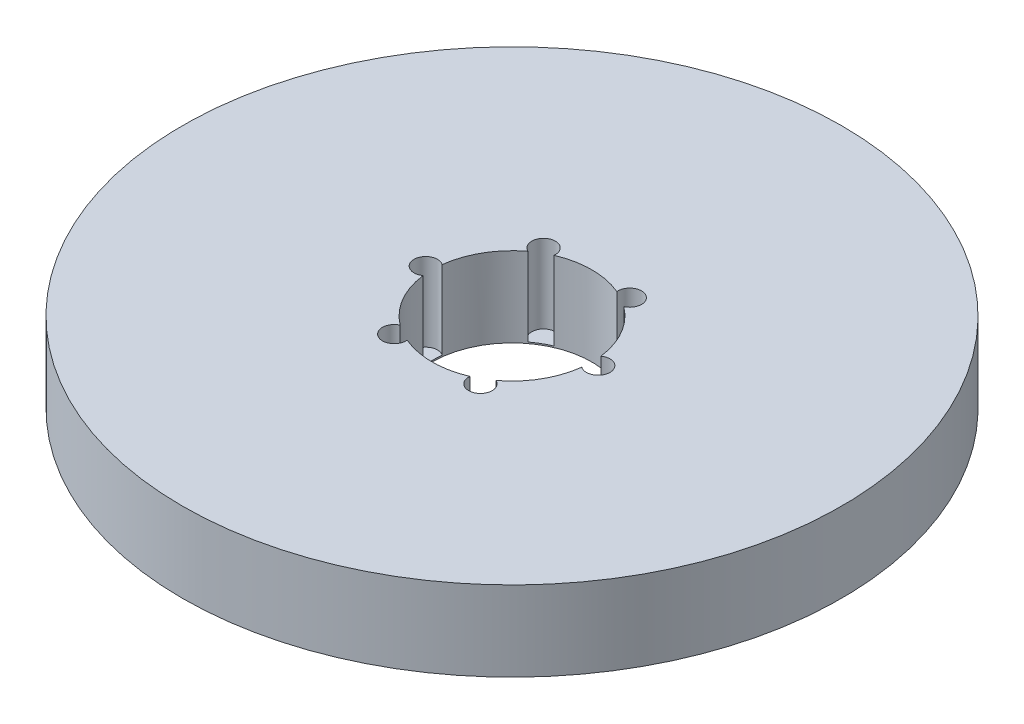
SolidWorks part; units mm, degrees
ref_plane "Front Plane" through (0, 0, 0) normal (0, 0, 1) x (1, 0, 0)
ref_plane "Top Plane" through (0, 0, 0) normal (0, 1, 0) x (1, 0, 0)
ref_plane "Right Plane" through (0, 0, 0) normal (1, 0, 0) x (0, 0, -1)
sketch "Sketch1" plane through (0, 0, 0) normal (0, 1, 0) x (1, 0, 0)
  circle A0 centre (0, 0) radius 82.5
  dimension "FLANGE_OD" = 165
extrude "Boss-Extrude1" add sketch "Sketch1" along normal blind 20
sketch "Sketch2" plane through (0, 0, 0) normal (0, 1, 0) x (1, 0, 0)
  circle A0 centre (0, 0) radius 20
  dimension "BORE_D" = 40
extrude "Cut-Extrude1" cut sketch "Sketch2" along normal through all
sketch "Sketch3" plane through (0, 20, 0) normal (0, 1, 0) x (1, 0, 0)
  circle A0 centre (0, 0) radius 21.5813 construction
  circle A1 centre (-21.5813, 0) radius 2.9471
  dimension "BOLT_D" = 5.8941
  dimension "BOLT_PCD" = 43.1626
extrude "Cut-Extrude2" cut sketch "Sketch3" against normal blind 19.6627
pattern_circular "CirPattern1" count 6 over 360 about axis through (0, 0, 0) along (0, 1, 0) of "Cut-Extrude2"
